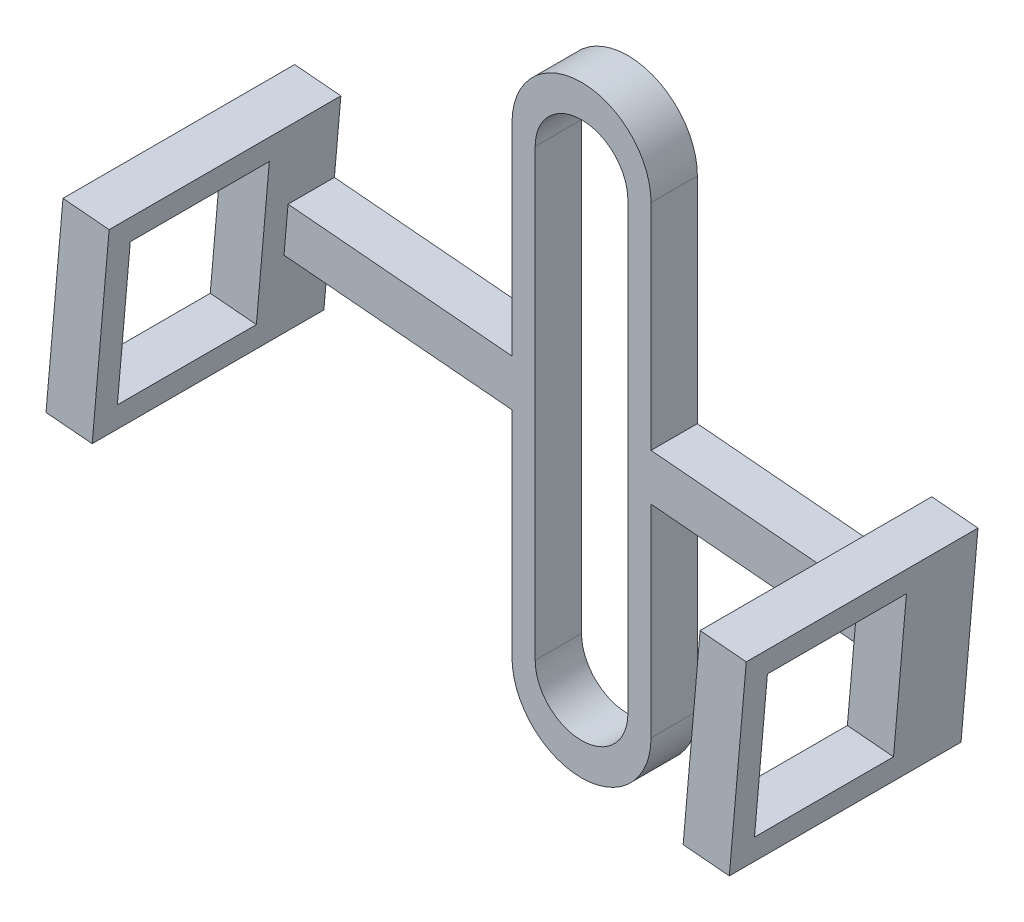
SolidWorks part; units mm, degrees
ref_plane "Front Plane" through (0, 0, 0) normal (0, 0, 1) x (1, 0, 0)
ref_plane "Top Plane" through (0, 0, 0) normal (0, 1, 0) x (1, 0, 0)
ref_plane "Right Plane" through (0, 0, 0) normal (1, 0, 0) x (0, 0, -1)
sketch "Sketch1" plane through (0, 0, 0) normal (0, 0, 1) x (1, 0, 0)
  line L1 (-9.525, -31.75) -> (9.525, -31.75)
  line L2 (-9.525, -31.75) -> (-9.525, 31.75)
  line L3 (-9.525, 31.75) -> (9.525, 31.75)
  line L4 (9.525, -31.75) -> (9.525, 31.75)
  line L5 (-9.525, -31.75) -> (9.525, 31.75) construction
  line L6 (-9.525, 31.75) -> (9.525, -31.75) construction
  circle A0 centre (0, 31.75) radius 9.525
  circle A1 centre (0, -31.75) radius 9.525
  point P0 (0, 0)
  dimension "D1" = 19.05
  dimension "D2" = 63.5
extrude "Boss-Extrude1" add sketch "Sketch1" along normal blind 6.35 contours A0 | L2 L1 L4 L3 | A1
sketch "Sketch2" plane through (0, 0, 6.35) normal (0, 0, 1) x (1, 0, 0)
  line L1 (-6.35, -30.48) -> (6.35, -30.48)
  line L2 (-6.35, -30.48) -> (-6.35, 30.48)
  line L3 (-6.35, 30.48) -> (6.35, 30.48)
  line L4 (6.35, -30.48) -> (6.35, 30.48)
  line L5 (-6.35, -30.48) -> (6.35, 30.48) construction
  line L6 (-6.35, 30.48) -> (6.35, -30.48) construction
  circle A0 centre (0, 30.48) radius 6.35
  circle A1 centre (0, -30.48) radius 6.35
  point P0 (0, 0)
  dimension "D1" = 12.7
  dimension "D2" = 60.96
extrude "Cut-Extrude1" cut sketch "Sketch2" against normal through all contours A0 | L2 L1 L4 L3 | A1
sketch "Sketch3" plane through (0, 0, 0) normal (0, 0, -1) x (-1, 0, 0)
  line L0 (-9.525, -31.75) -> (-9.525, 31.75) construction
  line L1 (46.5345, 7.2584) -> (-47.0879, -0.9325)
  line L2 (46.5345, 7.2584) -> (47.0879, 0.9325)
  line L3 (47.0879, 0.9325) -> (-46.5345, -7.2584)
  line L4 (-47.0879, -0.9325) -> (-46.5345, -7.2584)
  line L5 (-46.8112, -4.0954) -> (46.8112, 4.0954) construction
  point P4 (48.9382, 3.175)
  point P5 (46.99, 0)
  point P8 (0, 0)
  point P9 (-9.525, 0)
  point P10 (46.8725, 1.5426)
  point P12 (0, 0)
  dimension "D1" = 6.35
  dimension "D2" = 93.98
  dimension "D3" = 95
extrude "Boss-Extrude2" add sketch "Sketch3" against normal up to surface (6.35 mm away) up to face at (0, 0, 6.35)
sketch "Sketch7" plane through (0, 0, 6.35) normal (0, 0, 1) x (1, 0, 0)
  line L0 (-6.35, 3.7427) -> (6.35, 2.6316) construction
  line L1 (-6.35, 3.7427) -> (6.35, 2.6316)
  line L2 (-6.35, 3.7427) -> (-6.35, -2.6316)
  line L3 (-6.35, -2.6316) -> (6.35, -3.7427)
  line L4 (6.35, 2.6316) -> (6.35, -3.7427)
  point P6 (-6.35, -3.7427)
  point P8 (6.35, 3.7427)
extrude "Cut-Extrude3" cut sketch "Sketch7" against normal through all
sketch "Sketch4" plane through (-46.8112, 4.0954, 0) normal (0.9962, -0.0872, 0) x (0, 0, -1)
  line L0 (0, 3.175) -> (0, 32.4593) construction
  line L1 (-31.75, -13.335) -> (0, -13.335)
  line L2 (-31.75, -13.335) -> (-31.75, 13.335)
  line L3 (-31.75, 13.335) -> (0, 13.335)
  line L4 (0, -13.335) -> (0, 13.335)
  line L5 (-31.75, -13.335) -> (0, 13.335) construction
  line L6 (-31.75, 13.335) -> (0, -13.335) construction
  line L7 (-6.35, 3.175) -> (-6.35, 32.4593) construction
  point P0 (-15.875, 0)
  point P9 (0, 0)
  dimension "D1" = 25.4
  dimension "D2" = 26.67
extrude "Boss-Extrude3" add sketch "Sketch4" along normal blind 6.35
sketch "Sketch5" plane through (-40.4854, 3.542, 0) normal (0.9962, -0.0872, 0) x (0, 0, -1)
  line L0 (-31.75, 13.335) -> (-31.75, -13.335) construction
  line L1 (-28.575, -10.16) -> (-9.525, -10.16)
  line L2 (-28.575, -10.16) -> (-28.575, 10.16)
  line L3 (-28.575, 10.16) -> (-9.525, 10.16)
  line L4 (-9.525, -10.16) -> (-9.525, 10.16)
  line L5 (-28.575, -10.16) -> (-9.525, 10.16) construction
  line L6 (-28.575, 10.16) -> (-9.525, -10.16) construction
  point P0 (-19.05, 0)
  point P5 (0, 0)
  point P7 (-19.4277, -0.3119)
  point P8 (-18.6733, 0)
  dimension "D1" = 19.05
  dimension "D2" = 20.32
  dimension "D3" = 3.175
extrude "Cut-Extrude2" cut sketch "Sketch5" against normal through all contours L3 L4 L1 L2
sketch "Sketch6" plane through (46.8112, -4.0954, 0) normal (0.9962, -0.0872, 0) x (0, 0, -1)
  line L0 (-28.575, -10.16) -> (-9.525, -10.16) construction
  line L1 (-28.575, -10.16) -> (-28.575, 10.16) construction
  line L2 (-28.575, 10.16) -> (-9.525, 10.16) construction
  line L3 (-9.525, -10.16) -> (-9.525, 10.16) construction
  line L4 (-28.575, -10.16) -> (-9.525, -10.16)
  line L5 (-28.575, -10.16) -> (-28.575, 10.16)
  line L6 (-28.575, 10.16) -> (-9.525, 10.16)
  line L7 (-9.525, -10.16) -> (-9.525, 10.16)
  line L8 (-6.35, 3.175) -> (0, 3.175)
  line L9 (0, 3.175) -> (0, 13.335)
  line L10 (0, 13.335) -> (-31.75, 13.335)
  line L11 (-31.75, 13.335) -> (-31.75, -13.335)
  line L12 (-31.75, -13.335) -> (0, -13.335)
  line L13 (0, -13.335) -> (0, -3.175)
  line L14 (0, -3.175) -> (-6.35, -3.175)
  line L15 (-6.35, -3.175) -> (-6.35, 3.175)
  line L16 (-6.35, 3.175) -> (0, 3.175)
  line L17 (0, 3.175) -> (0, 13.335)
  line L18 (0, 13.335) -> (-31.75, 13.335)
  line L19 (-31.75, 13.335) -> (-31.75, -13.335)
  line L20 (-31.75, -13.335) -> (0, -13.335)
  line L21 (0, -13.335) -> (0, -3.175)
  line L22 (0, -3.175) -> (-6.35, -3.175)
  line L23 (-6.35, -3.175) -> (-6.35, 3.175)
  dimension "D1" = 0
extrude "Boss-Extrude4" add sketch "Sketch6" against normal blind 6.35
